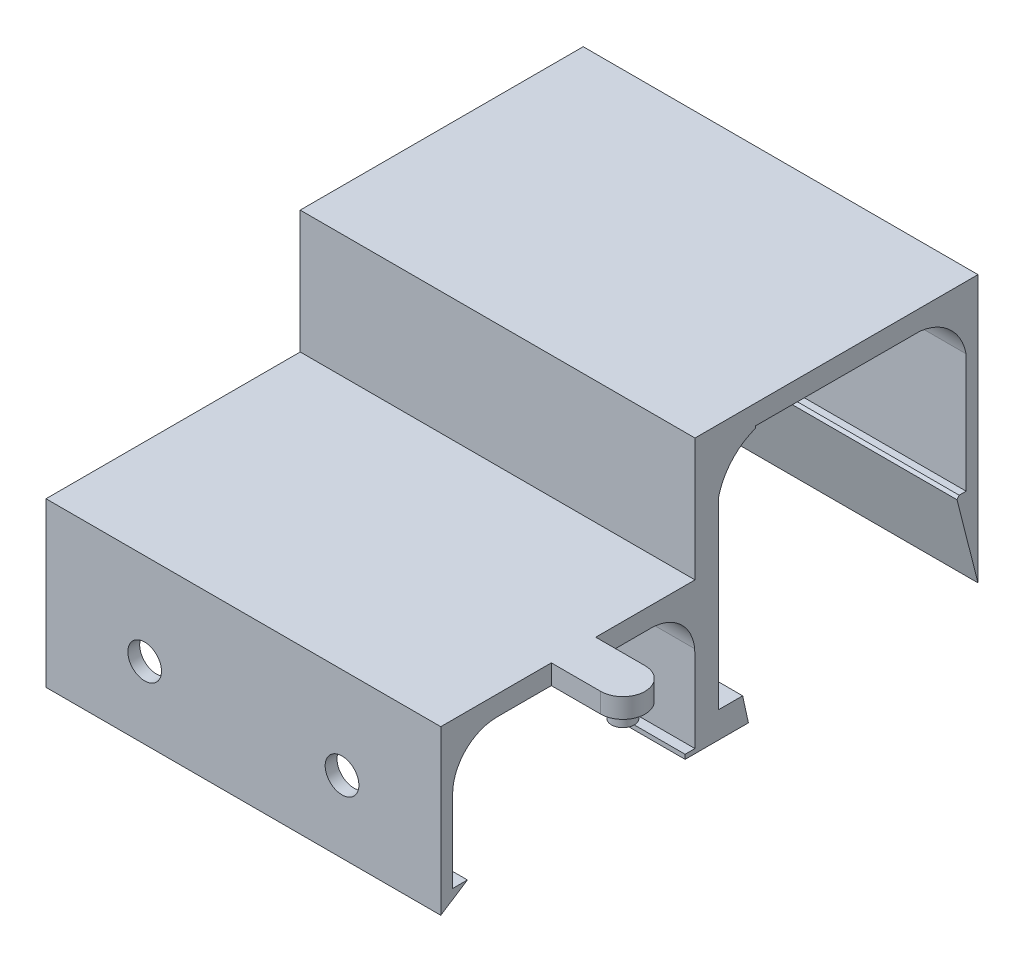
SolidWorks part; units mm, degrees
ref_plane "Front Plane" through (0, 0, 0) normal (0, 0, 1) x (1, 0, 0)
ref_plane "Top Plane" through (0, 0, 0) normal (0, 1, 0) x (1, 0, 0)
ref_plane "Right Plane" through (0, 0, 0) normal (1, 0, 0) x (0, 0, -1)
sketch "Sketch1" plane through (0, 0, 0) normal (1, 0, 0) x (0, 0, -1)
  line L0 (-187.4725, -316.8156) -> (-187.4725, -325.1157)
  line L5 (-187.4725, -325.1157) -> (-185.9725, -325.1157)
  line L7 (-185.9725, -325.1157) -> (-188.6725, -326.869)
  line L8 (-188.6725, -326.869) -> (-188.6725, -312.3156)
  line L9 (-188.6725, -310.3156) -> (-162.9159, -310.3156)
  line L10 (-188.6725, -310.3156) -> (-188.6725, -312.3156)
  line L11 (-162.9159, -325.5656) -> (-157.5031, -325.5656)
  line L12 (-162.9159, -325.1157) -> (-163.9159, -325.1157)
  line L13 (-182.9725, -312.3156) -> (-167.4159, -312.3156)
  line L14 (-163.9159, -325.1157) -> (-163.9159, -325.5656)
  line L16 (-163.9159, -325.5656) -> (-162.9159, -325.5656)
  line L17 (-157.5031, -325.5656) -> (-158.0849, -322.9014)
  line L18 (-158.0849, -322.9014) -> (-160.5558, -322.9014)
  line L19 (-160.5558, -322.9014) -> (-160.5558, -304.3701)
  line L20 (-162.9159, -310.3156) -> (-162.9159, -297.8657)
  line L21 (-162.9159, -297.8657) -> (-134.2405, -297.8657)
  line L22 (-134.2405, -297.8657) -> (-134.2405, -324.9156)
  line L23 (-134.2405, -324.9156) -> (-136.3676, -316.5568)
  line L24 (-136.3676, -316.5568) -> (-136.1447, -316.2701)
  line L25 (-136.1447, -316.2701) -> (-135.4405, -316.2701)
  line L26 (-135.4405, -316.2701) -> (-135.4405, -304.2217)
  line L27 (-156.7631, -300.0668) -> (-156.7631, -299.8657)
  line L28 (-156.7631, -299.8657) -> (-140.0814, -299.8931)
  line L29 (-162.9406, -316.3453) -> (-162.9159, -325.1157)
  arc A0 (-187.4725, -316.8156) -> (-182.9725, -312.3156) centre (-182.9725, -316.8156) cw
  arc A1 (-140.0814, -299.8931) -> (-135.4405, -304.2217) centre (-140.7448, -305.2565) cw
  arc A2 (-160.5558, -304.3701) -> (-156.7631, -300.0668) centre (-154.7245, -305.6865) cw
  arc A3 (-167.4159, -312.3156) -> (-162.9406, -316.3453) centre (-167.4159, -316.8157) cw
  point P3 (0, 0)
  point P8 (0, 0)
  point P9 (0, 0)
  point P35 (0, 0)
  point P36 (0, 0)
  point P37 (0, 0)
  point P38 (0, 0)
  point P39 (0, 0)
  point P40 (0, 0)
  point P41 (0, 0)
  point P42 (0, 0)
  point P43 (0, 0)
  point P44 (0, 0)
  point P45 (0, 0)
  point P46 (0, 0)
  point P47 (0, 0)
  point P48 (0, 0)
  point P49 (0, 0)
  point P50 (0, 0)
  point P51 (0, 0)
  point P52 (0, 0)
  point P53 (0, 0)
  point P54 (0, 0)
  point P55 (0, 0)
  point P56 (0, 0)
  point P57 (0, 0)
  point P58 (0, 0)
extrude "Boss-Extrude1" add sketch "Sketch1" along normal blind 20 and the other way blind 20
sketch "Sketch2" plane through (0, -310.3156, 0) normal (0, 1, 0) x (1, 0, 0)
  line L1 (20, -172.9725) -> (25, -172.9725)
  line L2 (20, -172.9725) -> (20, -177.4725)
  line L3 (20, -177.4725) -> (25, -177.4725)
  arc A0 (25, -172.9725) -> (25, -177.4725) centre (25, -175.2225) cw
  point P7 (0, 0)
  point P8 (0, 0)
extrude "Boss-Extrude2" add sketch "Sketch2" against normal blind 2
sketch "Sketch3" plane through (0, -312.3156, 0) normal (0, -1, 0) x (1, 0, 0)
  circle A0 centre (25, 175.2225) radius 1.15
extrude "Boss-Extrude3" add sketch "Sketch3" along normal blind 1.5
sketch "Sketch4" plane through (0, 0, 134.2405) normal (0, 0, -1) x (-1, 0, 0)
  line L0 (20, -324.9156) -> (20, -297.8657) construction
  circle A0 centre (0, -310.0156) radius 4.175
  point P9 (-59.0441, -288.3072)
  dimension "D1" = 20
extrude "Cut-Extrude2" cut sketch "Sketch4" against normal blind 2
sketch "Sketch5" plane through (0, 0, 188.6725) normal (0, 0, 1) x (1, 0, 0)
  circle A0 centre (-10.0037, -319.5977) radius 1.7052
  circle A1 centre (9.9933, -319.6) radius 1.7075
  dimension "D3" = 19.997
extrude "Cut-Extrude4" cut sketch "Sketch5" against normal blind 2
